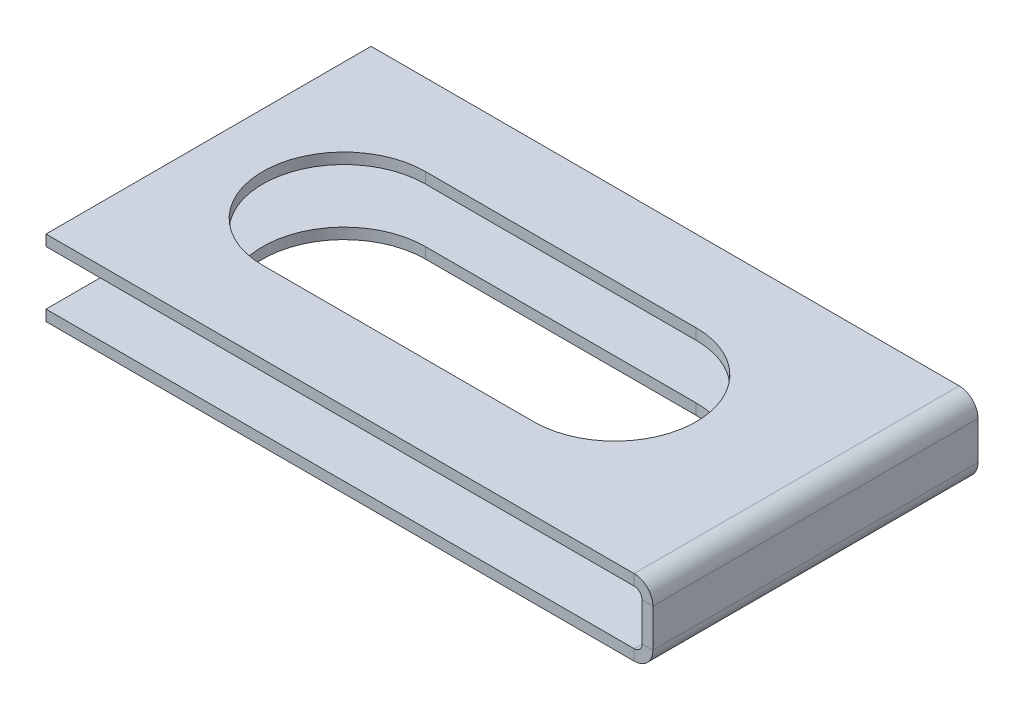
SolidWorks part; units mm, degrees
note: The reader was unsure of these and kept them because the rebuilt part matched: flange length of "Tôle pliée sur arête1", "Tôle pliée sur arête2".
ref_plane "Plan de face" through (0, 0, 0) normal (0, 0, 1) x (1, 0, 0)
ref_plane "Plan de dessus" through (0, 0, 0) normal (0, 1, 0) x (1, 0, 0)
ref_plane "Plan de droite" through (0, 0, 0) normal (1, 0, 0) x (0, 0, -1)
sketch "Esquisse2" plane through (0, 0, 0) normal (0, 1, 0) x (1, 0, 0)
  line L1 (-27.5, -15) -> (27.5, -15)
  line L2 (-27.5, -15) -> (-27.5, 15)
  line L3 (-27.5, 15) -> (27.5, 15)
  line L4 (27.5, -15) -> (27.5, 15)
  line L5 (-27.5, -15) -> (27.5, 15) construction
  line L6 (-27.5, 15) -> (27.5, -15) construction
  line L9 (-7.8646, 0) -> (7.8646, 0) construction
  point P0 (0, 0)
  dimension "D130" = 30
  dimension "D2" = 55
base flange "Tôle de base pliée1" sketch "Esquisse2" thickness 1 reverse thickness direction no parameters "D1"=0.7366
edge flange "Tôle pliée sur arête1" sketch "Esquisse9" flange angle 90 flange length 5 flange position material outside bend radius 0.7366 thickness 1 relief rectangular parameters "D6"=10
sketch "Esquisse9" plane through (27.5, -1, 0) normal (1, 0, 0) x (0, 0, 1)
  line L2 (-15, 0) -> (-15, 5)
  line L3 (-15, 5) -> (15, 5)
  line L4 (15, 5) -> (15, 0)
  line L7 (15, 0) -> (-15, 0) construction
  line L8 (15, 0) -> (-15, 0)
bend "Pli d'arête1" bend radius 0.7366 bend angle 90 parameters "D5"=1
edge flange "Tôle pliée sur arête2" sketch "Esquisse12" flange angle 90 flange length 55 flange position material outside bend radius 0.7366 thickness 1 relief rectangular parameters "D6"=10
sketch "Esquisse12" plane through (27.5, -6, 0) normal (0, -1, 0) x (0, 0, 1)
  line L0 (15, 0) -> (-15, 0) construction
  line L1 (15, 0) -> (-15, 0)
  line L2 (-15, 0) -> (-15, 55)
  line L3 (-15, 55) -> (15, 55)
  line L4 (15, 55) -> (15, 0)
bend "Pli d'arête2" bend radius 0.7366 bend angle 90 parameters "D5"=2
sketch "Esquisse26" plane through (0, 0, 0) normal (0, 1, 0) x (1, 0, 0)
  line L0 (-15, 0) -> (10, 0) construction
  line L1 (-7.8646, 0) -> (7.8646, 0) construction
  line L2 (-15, 7.5) -> (10, 7.5)
  line L3 (-15, -7.5) -> (10, -7.5)
  line L7 (-27.5, 15) -> (-27.5, -15) construction
  arc A0 (-15, 7.5) -> (-15, -7.5) centre (-15, 0) ccw
  arc A1 (10, -7.5) -> (10, 7.5) centre (10, 0) ccw
  point P5 (-2.5, 0)
  point P10 (-22.5, 0)
  point P11 (17.5, 0)
  dimension "D1" = 40
  dimension "D2" = 15
  dimension "D3" = 5
extrude "Enlèv. mat.-Extru.1" cut sketch "Esquisse26" against normal through all normal cut yes
sketch "Esquisse29" plane through (0, -6, 0) normal (0, 1, 0) x (1, 0, 0)
  line L0 (-7.8646, 0) -> (7.8646, 0) construction
  line L1 (28.5, -15) -> (28.5, 15) construction
  circle A0 centre (24, 0) radius 1.7
  dimension "D1" = 3.4
  dimension "D2" = 4.5
extrude "Enlèv. mat.-Extru.3" cut sketch "Esquisse29" against normal through all normal cut yes
sketch "Esquisse30" plane through (0, -7, 0) normal (0, -1, 0) x (1, 0, 0)
  line L0 (-2.5, 7.5) -> (-2.5, -7.5) construction
  line L1 (-15, 7.5) -> (10, 7.5) construction
  line L2 (10, -7.5) -> (-15, -7.5) construction
sketch3d "Esquisse3D2"
  line L0 (-2.5, -7, 7.5) -> (-2.5, -7, -7.5) construction
sketch "Lignes de pliage1" [suppressed] plane through (0, 0, 0) normal (0, 1, 0) x (1, 0, 0)
sketch "Cube de visualisation1" [suppressed] plane through (0, 0, 0) normal (0, 1, 0) x (1, 0, 0)
sheet metal parameters "Tôlerie1" thickness 1 parameters "D1"=0.7366
flat pattern "Etat déplié1" [suppressed]
sketch "Lignes de pliage2" plane through (0, 0, 0) normal (0, 1, 0) x (1, 0, 0)
sketch3d "Cube de visualisation2" [suppressed]
  line L0 (-26.75, 15, 0) -> (26.75, 15, 0) construction
  line L1 (-26.75, -15, 0) -> (26.75, -15, 0) construction
  line L2 (-26.75, 15, 0) -> (-26.75, -15, 0) construction
  line L3 (26.75, 15, 0) -> (26.75, -15, 0) construction
sheet metal parameters "Tôlerie2" thickness 1 parameters "D1"=0.7366
flat pattern "Etat déplié1"
sketch "Lignes de pliage2" plane through (0, 0, 0) normal (0, 1, 0) x (1, 0, 0)
  line L0 (26.9846, -15) -> (26.9846, 15) construction
  line L1 (26.9846, -15) -> (26.9846, 15) construction
sketch3d "Cube de visualisation2" [suppressed]
  line L0 (32.2192, 15, 0) -> (-26.75, 15, 0) construction
  line L1 (32.2192, -15, 0) -> (-26.75, -15, 0) construction
  line L2 (32.2192, 15, 0) -> (32.2192, -15, 0) construction
  line L3 (-26.75, 15, 0) -> (-26.75, -15, 0) construction
bend of the flat pattern "Dépliage-<Pli d'arête1>1"
sheet metal parameters "Tôlerie3" thickness 1 parameters "D1"=0.7366
flat pattern "Etat déplié1"
sketch "Lignes de pliage2" plane through (0, 0, 0) normal (0, 1, 0) x (1, 0, 0)
  line L0 (26.9846, -15) -> (26.9846, 15) construction
  line L1 (26.9846, -15) -> (26.9846, 15) construction
  line L2 (32.4539, -15) -> (32.4539, 15) construction
  line L3 (32.4539, -15) -> (32.4539, 15) construction
sketch3d "Cube de visualisation2" [suppressed]
  line L0 (86.1885, 15, 0) -> (-26.75, 15, 0) construction
  line L1 (86.1885, -15, 0) -> (-26.75, -15, 0) construction
  line L2 (86.1885, 15, 0) -> (86.1885, -15, 0) construction
  line L3 (-26.75, 15, 0) -> (-26.75, -15, 0) construction
bend of the flat pattern "Dépliage-<Pli d'arête1>1"
bend of the flat pattern "Dépliage-<Pli d'arête2>1"
sheet metal parameters "Tôlerie7" thickness 1 parameters "D1"=0.7366
flat pattern "Etat déplié1"
sketch "Lignes de pliage2" plane through (0, 0, 0) normal (0, 1, 0) x (1, 0, 0)
  line L0 (26.9846, -15) -> (26.9846, 15) construction
  line L1 (26.9846, -15) -> (26.9846, 15) construction
  line L2 (32.4539, -15) -> (32.4539, 15) construction
  line L3 (32.4539, -15) -> (32.4539, 15) construction
sketch3d "Cube de visualisation2" [suppressed]
  line L0 (86.1885, 15, 0) -> (-26.75, 15, 0) construction
  line L1 (86.1885, -15, 0) -> (-26.75, -15, 0) construction
  line L2 (86.1885, 15, 0) -> (86.1885, -15, 0) construction
  line L3 (-26.75, 15, 0) -> (-26.75, -15, 0) construction
bend of the flat pattern "Dépliage-<Pli d'arête1>1"
bend of the flat pattern "Dépliage-<Pli d'arête2>1"
sheet metal parameters "Tôlerie9" thickness 1 parameters "D1"=0.7366
flat pattern "Etat déplié1" [suppressed]
sketch "Lignes de pliage2" plane through (0, 0, 0) normal (0, 1, 0) x (1, 0, 0)
  line L0 (27.7346, -15) -> (27.7346, 15) construction
  line L1 (27.7346, -15) -> (27.7346, 15) construction
  line L2 (33.2039, -15) -> (33.2039, 15) construction
  line L3 (33.2039, -15) -> (33.2039, 15) construction
sketch3d "Cube de visualisation2" [suppressed]
  line L0 (88.4385, 15, 0) -> (-27.5, 15, 0) construction
  line L1 (88.4385, -15, 0) -> (-27.5, -15, 0) construction
  line L2 (88.4385, 15, 0) -> (88.4385, -15, 0) construction
  line L3 (-27.5, 15, 0) -> (-27.5, -15, 0) construction
bend of the flat pattern "Dépliage-<Pli d'arête1>1"
bend of the flat pattern "Dépliage-<Pli d'arête2>1"
sketch "Esquisse30-1" plane through (60.9385, 0, 0) normal (0, 1, 0) x (-1, 0, 0)
  line L0 (-2.5, 7.5) -> (-2.5, -7.5) construction
